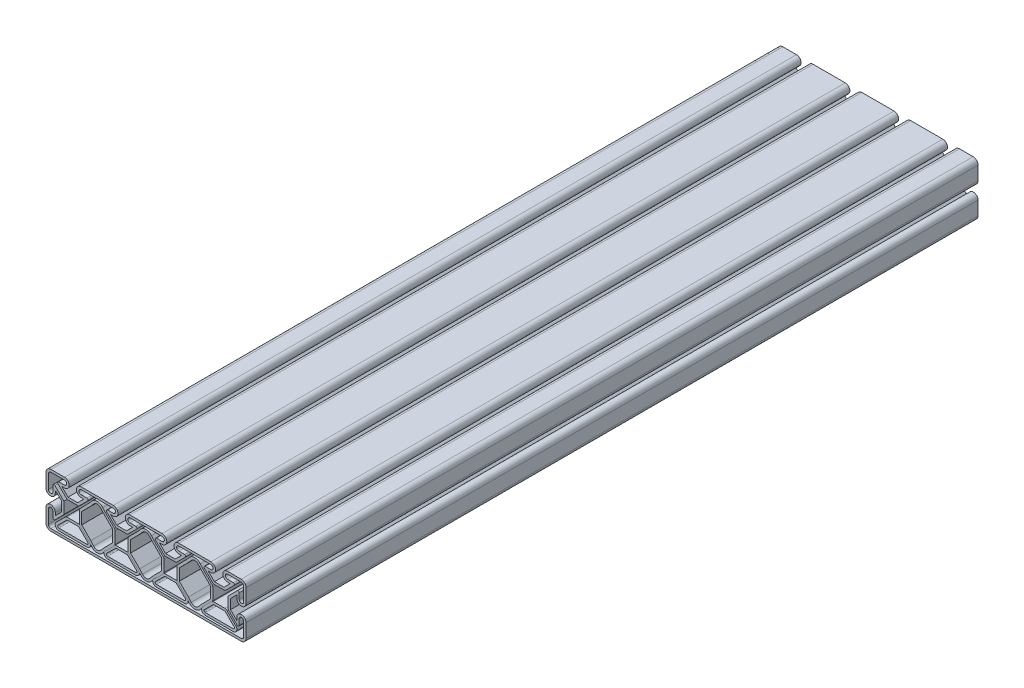
SolidWorks part; units mm, degrees
ref_plane "Alzado" through (0, 0, 0) normal (0, 0, 1) x (1, 0, 0)
ref_plane "Planta" through (0, 0, 0) normal (0, 1, 0) x (1, 0, 0)
ref_plane "Vista Lateral" through (0, 0, 0) normal (1, 0, 0) x (0, 0, -1)
ref_plane "Plano1" through (0, 0, 50) normal (0, 0, 1) x (1, 0, 0)
sketch "Croquis1" plane through (0, 0, 50) normal (0, 0, 1) x (1, 0, 0)
  line L0 (2.5926, -6.0784) -> (1.4258, -7.4138)
  line L1 (-1.5144, -7.3727) -> (-2.6752, -6.0808)
  line L2 (-2.6961, -6.061) -> (-6.3866, -2.3416)
  line L3 (-6.3926, -2.3074) -> (-6.3926, 2.3926)
  line L4 (-6.3866, 2.4268) -> (-2.6961, 6.1461)
  line L5 (-2.6778, 6.1636) -> (-1.511, 7.499)
  line L6 (1.4293, 7.4579) -> (2.59, 6.166)
  line L7 (2.611, 6.1461) -> (6.3014, 2.4268)
  line L8 (6.3074, 2.3926) -> (6.3074, -2.3074)
  line L9 (6.3014, -2.3416) -> (2.611, -6.061)
  line L10 (6.5574, 10.0426) -> (-6.6426, 10.0426)
  line L11 (-6.6426, 8.2426) -> (-4.2926, 8.2426)
  line L12 (-3.939, 7.389) -> (-7.5986, 3.7584)
  line L13 (-7.6926, 3.6926) -> (-12.3926, 3.6926)
  line L14 (-12.4866, 3.7584) -> (-16.1461, 7.389)
  line L15 (-15.7926, 8.2426) -> (-13.4426, 8.2426)
  line L16 (-13.4426, 10.0426) -> (-26.6426, 10.0426)
  line L17 (-26.6426, 8.2426) -> (-24.2926, 8.2426)
  line L18 (-23.939, 7.389) -> (-27.5986, 3.7584)
  line L19 (-27.6926, 3.6926) -> (-32.3926, 3.6926)
  line L20 (-32.4866, 3.7584) -> (-36.1461, 7.389)
  line L21 (-35.7926, 8.2426) -> (-33.4426, 8.2426)
  line L22 (-33.4426, 10.0426) -> (-39.0426, 10.0426)
  line L23 (-40.0426, 9.0426) -> (-40.0426, 3.4426)
  line L24 (-38.2426, 3.4426) -> (-38.2426, 5.7926)
  line L25 (-37.389, 6.1461) -> (-33.6986, 2.4268)
  line L26 (-33.6926, 2.3926) -> (-33.6926, -2.3074)
  line L27 (-33.6986, -2.3416) -> (-37.389, -6.061)
  line L28 (-38.2426, -5.7074) -> (-38.2426, -3.3574)
  line L29 (-40.0426, -3.3574) -> (-40.0426, -8.9574)
  line L30 (-39.0426, -9.9574) -> (-33.4426, -9.9574)
  line L31 (-33.4426, -8.1574) -> (-35.7926, -8.1574)
  line L32 (-36.1461, -7.3039) -> (-32.4866, -3.6732)
  line L33 (-32.3926, -3.6074) -> (-27.6926, -3.6074)
  line L34 (-27.5986, -3.6732) -> (-23.939, -7.3039)
  line L35 (-24.2926, -8.1574) -> (-26.6426, -8.1574)
  line L36 (-26.6426, -9.9574) -> (-13.4426, -9.9574)
  line L37 (-13.4426, -8.1574) -> (-15.7926, -8.1574)
  line L38 (-16.1461, -7.3039) -> (-12.4866, -3.6732)
  line L39 (-12.3926, -3.6074) -> (-7.6926, -3.6074)
  line L40 (-7.5986, -3.6732) -> (-3.939, -7.3039)
  line L41 (-4.2926, -8.1574) -> (-6.6426, -8.1574)
  line L42 (-6.6426, -9.9574) -> (6.5574, -9.9574)
  line L43 (6.5574, -8.1574) -> (4.2074, -8.1574)
  line L44 (3.8539, -7.3039) -> (7.5134, -3.6732)
  line L45 (7.6074, -3.6074) -> (12.3074, -3.6074)
  line L46 (12.4014, -3.6732) -> (16.061, -7.3039)
  line L47 (15.7074, -8.1574) -> (13.3574, -8.1574)
  line L48 (13.3574, -9.9574) -> (26.5574, -9.9574)
  line L49 (26.5574, -8.1574) -> (24.2074, -8.1574)
  line L50 (23.8539, -7.3039) -> (27.5134, -3.6732)
  line L51 (27.6074, -3.6074) -> (32.3074, -3.6074)
  line L52 (32.4014, -3.6732) -> (36.061, -7.3039)
  line L53 (35.7074, -8.1574) -> (33.3574, -8.1574)
  line L54 (33.3574, -9.9574) -> (38.9574, -9.9574)
  line L55 (39.9574, -8.9574) -> (39.9574, -3.3574)
  line L56 (38.1574, -3.3574) -> (38.1574, -5.7074)
  line L57 (37.3039, -6.061) -> (33.6134, -2.3416)
  line L58 (33.6074, -2.3074) -> (33.6074, 2.3926)
  line L59 (33.6134, 2.4268) -> (37.3039, 6.1461)
  line L60 (38.1574, 5.7926) -> (38.1574, 3.4426)
  line L61 (39.9574, 3.4426) -> (39.9574, 9.0426)
  line L62 (38.9574, 10.0426) -> (33.3574, 10.0426)
  line L63 (33.3574, 8.2426) -> (35.7074, 8.2426)
  line L64 (36.061, 7.389) -> (32.4014, 3.7584)
  line L65 (32.3074, 3.6926) -> (27.6074, 3.6926)
  line L66 (27.5134, 3.7584) -> (23.8539, 7.389)
  line L67 (24.2074, 8.2426) -> (26.5574, 8.2426)
  line L68 (26.5574, 10.0426) -> (13.3574, 10.0426)
  line L69 (13.3574, 8.2426) -> (15.7074, 8.2426)
  line L70 (16.061, 7.389) -> (12.4014, 3.7584)
  line L71 (12.3074, 3.6926) -> (7.6074, 3.6926)
  line L72 (7.5134, 3.7584) -> (3.8539, 7.389)
  line L73 (4.2074, 8.2426) -> (6.5574, 8.2426)
  line L74 (-17.4074, -6.0784) -> (-18.5742, -7.4138)
  line L75 (-21.5144, -7.3727) -> (-22.6752, -6.0808)
  line L76 (-22.6961, -6.061) -> (-26.3866, -2.3416)
  line L77 (-26.3926, -2.3074) -> (-26.3926, 2.3926)
  line L78 (-26.3866, 2.4268) -> (-22.6961, 6.1461)
  line L79 (-22.6778, 6.1636) -> (-21.511, 7.499)
  line L80 (-18.5707, 7.4579) -> (-17.41, 6.166)
  line L81 (-17.389, 6.1461) -> (-13.6986, 2.4268)
  line L82 (-13.6926, 2.3926) -> (-13.6926, -2.3074)
  line L83 (-13.6986, -2.3416) -> (-17.389, -6.061)
  line L84 (17.3222, 6.1636) -> (18.489, 7.499)
  line L85 (21.4293, 7.4579) -> (22.59, 6.166)
  line L86 (22.611, 6.1461) -> (26.3014, 2.4268)
  line L87 (26.3074, 2.3926) -> (26.3074, -2.3074)
  line L88 (26.3014, -2.3416) -> (22.611, -6.061)
  line L89 (22.5926, -6.0784) -> (21.4258, -7.4138)
  line L90 (18.4856, -7.3727) -> (17.3248, -6.0808)
  line L91 (17.3039, -6.061) -> (13.6134, -2.3416)
  line L92 (13.6074, -2.3074) -> (13.6074, 2.3926)
  line L93 (13.6134, 2.4268) -> (17.3039, 6.1461)
  line L94 (-33.4426, -8.1574) -> (-26.6426, -8.1574)
  line L95 (-26.6426, -9.9574) -> (-33.4426, -9.9574)
  line L96 (26.5574, -8.1574) -> (33.3574, -8.1574)
  line L97 (33.3574, -9.9574) -> (26.5574, -9.9574)
  line L98 (-13.4426, -8.1574) -> (-6.6426, -8.1574)
  line L99 (-13.4426, -9.9574) -> (-6.6426, -9.9574)
  line L100 (6.5574, -8.1574) -> (13.3574, -8.1574)
  line L101 (6.5574, -9.9574) -> (13.3574, -9.9574)
  arc A0 (1.4258, -7.4138) -> (-1.5144, -7.3727) centre (-0.0284, -6.257) cw
  arc A1 (-2.6752, -6.0808) -> (-2.6961, -6.061) centre (-2.3426, -5.7074) cw
  arc A2 (-6.3866, -2.3416) -> (-6.3926, -2.3074) centre (-6.2926, -2.3074) cw
  arc A3 (-6.3926, 2.3926) -> (-6.3866, 2.4268) centre (-6.2926, 2.3926) cw
  arc A4 (-2.6961, 6.1461) -> (-2.6778, 6.1636) centre (-2.3426, 5.7926) cw
  arc A5 (-1.511, 7.499) -> (1.4293, 7.4579) centre (-0.0568, 6.3422) cw
  arc A6 (2.59, 6.166) -> (2.611, 6.1461) centre (2.2574, 5.7926) cw
  arc A7 (6.3014, 2.4268) -> (6.3074, 2.3926) centre (6.2074, 2.3926) cw
  arc A8 (6.3074, -2.3074) -> (6.3014, -2.3416) centre (6.2074, -2.3074) cw
  arc A9 (2.611, -6.061) -> (2.5926, -6.0784) centre (2.2574, -5.7074) cw
  arc A10 (6.5574, 8.2426) -> (6.5574, 10.0426) centre (6.5574, 9.1426) ccw
  arc A11 (-6.6426, 10.0426) -> (-6.6426, 8.2426) centre (-6.6426, 9.1426) ccw
  arc A12 (-4.2926, 8.2426) -> (-3.939, 7.389) centre (-4.2926, 7.7426) cw
  arc A13 (-7.5986, 3.7584) -> (-7.6926, 3.6926) centre (-7.6926, 3.7926) cw
  arc A14 (-12.3926, 3.6926) -> (-12.4866, 3.7584) centre (-12.3926, 3.7926) cw
  arc A15 (-16.1461, 7.389) -> (-15.7926, 8.2426) centre (-15.7926, 7.7426) cw
  arc A16 (-13.4426, 8.2426) -> (-13.4426, 10.0426) centre (-13.4426, 9.1426) ccw
  arc A17 (-26.6426, 10.0426) -> (-26.6426, 8.2426) centre (-26.6426, 9.1426) ccw
  arc A18 (-24.2926, 8.2426) -> (-23.939, 7.389) centre (-24.2926, 7.7426) cw
  arc A19 (-27.5986, 3.7584) -> (-27.6926, 3.6926) centre (-27.6926, 3.7926) cw
  arc A20 (-32.3926, 3.6926) -> (-32.4866, 3.7584) centre (-32.3926, 3.7926) cw
  arc A21 (-36.1461, 7.389) -> (-35.7926, 8.2426) centre (-35.7926, 7.7426) cw
  arc A22 (-33.4426, 8.2426) -> (-33.4426, 10.0426) centre (-33.4426, 9.1426) ccw
  arc A23 (-39.0426, 10.0426) -> (-40.0426, 9.0426) centre (-39.0426, 9.0426) ccw
  arc A24 (-40.0426, 3.4426) -> (-38.2426, 3.4426) centre (-39.1426, 3.4426) ccw
  arc A25 (-38.2426, 5.7926) -> (-37.389, 6.1461) centre (-37.7426, 5.7926) cw
  arc A26 (-33.6986, 2.4268) -> (-33.6926, 2.3926) centre (-33.7926, 2.3926) cw
  arc A27 (-33.6926, -2.3074) -> (-33.6986, -2.3416) centre (-33.7926, -2.3074) cw
  arc A28 (-37.389, -6.061) -> (-38.2426, -5.7074) centre (-37.7426, -5.7074) cw
  arc A29 (-38.2426, -3.3574) -> (-40.0426, -3.3574) centre (-39.1426, -3.3574) ccw
  arc A30 (-40.0426, -8.9574) -> (-39.0426, -9.9574) centre (-39.0426, -8.9574) ccw
  arc A31 (-35.7926, -8.1574) -> (-36.1461, -7.3039) centre (-35.7926, -7.6574) cw
  arc A32 (-32.4866, -3.6732) -> (-32.3926, -3.6074) centre (-32.3926, -3.7074) cw
  arc A33 (-27.6926, -3.6074) -> (-27.5986, -3.6732) centre (-27.6926, -3.7074) cw
  arc A34 (-23.939, -7.3039) -> (-24.2926, -8.1574) centre (-24.2926, -7.6574) cw
  arc A35 (-15.7926, -8.1574) -> (-16.1461, -7.3039) centre (-15.7926, -7.6574) cw
  arc A36 (-12.4866, -3.6732) -> (-12.3926, -3.6074) centre (-12.3926, -3.7074) cw
  arc A37 (-7.6926, -3.6074) -> (-7.5986, -3.6732) centre (-7.6926, -3.7074) cw
  arc A38 (-3.939, -7.3039) -> (-4.2926, -8.1574) centre (-4.2926, -7.6574) cw
  arc A39 (4.2074, -8.1574) -> (3.8539, -7.3039) centre (4.2074, -7.6574) cw
  arc A40 (7.5134, -3.6732) -> (7.6074, -3.6074) centre (7.6074, -3.7074) cw
  arc A41 (12.3074, -3.6074) -> (12.4014, -3.6732) centre (12.3074, -3.7074) cw
  arc A42 (16.061, -7.3039) -> (15.7074, -8.1574) centre (15.7074, -7.6574) cw
  arc A43 (24.2074, -8.1574) -> (23.8539, -7.3039) centre (24.2074, -7.6574) cw
  arc A44 (27.5134, -3.6732) -> (27.6074, -3.6074) centre (27.6074, -3.7074) cw
  arc A45 (32.3074, -3.6074) -> (32.4014, -3.6732) centre (32.3074, -3.7074) cw
  arc A46 (36.061, -7.3039) -> (35.7074, -8.1574) centre (35.7074, -7.6574) cw
  arc A47 (38.9574, -9.9574) -> (39.9574, -8.9574) centre (38.9574, -8.9574) ccw
  arc A48 (39.9574, -3.3574) -> (38.1574, -3.3574) centre (39.0574, -3.3574) ccw
  arc A49 (38.1574, -5.7074) -> (37.3039, -6.061) centre (37.6574, -5.7074) cw
  arc A50 (33.6134, -2.3416) -> (33.6074, -2.3074) centre (33.7074, -2.3074) cw
  arc A51 (33.6074, 2.3926) -> (33.6134, 2.4268) centre (33.7074, 2.3926) cw
  arc A52 (37.3039, 6.1461) -> (38.1574, 5.7926) centre (37.6574, 5.7926) cw
  arc A53 (38.1574, 3.4426) -> (39.9574, 3.4426) centre (39.0574, 3.4426) ccw
  arc A54 (39.9574, 9.0426) -> (38.9574, 10.0426) centre (38.9574, 9.0426) ccw
  arc A55 (33.3574, 10.0426) -> (33.3574, 8.2426) centre (33.3574, 9.1426) ccw
  arc A56 (35.7074, 8.2426) -> (36.061, 7.389) centre (35.7074, 7.7426) cw
  arc A57 (32.4014, 3.7584) -> (32.3074, 3.6926) centre (32.3074, 3.7926) cw
  arc A58 (27.6074, 3.6926) -> (27.5134, 3.7584) centre (27.6074, 3.7926) cw
  arc A59 (23.8539, 7.389) -> (24.2074, 8.2426) centre (24.2074, 7.7426) cw
  arc A60 (26.5574, 8.2426) -> (26.5574, 10.0426) centre (26.5574, 9.1426) ccw
  arc A61 (13.3574, 10.0426) -> (13.3574, 8.2426) centre (13.3574, 9.1426) ccw
  arc A62 (15.7074, 8.2426) -> (16.061, 7.389) centre (15.7074, 7.7426) cw
  arc A63 (12.4014, 3.7584) -> (12.3074, 3.6926) centre (12.3074, 3.7926) cw
  arc A64 (7.6074, 3.6926) -> (7.5134, 3.7584) centre (7.6074, 3.7926) cw
  arc A65 (3.8539, 7.389) -> (4.2074, 8.2426) centre (4.2074, 7.7426) cw
  arc A66 (-18.5742, -7.4138) -> (-21.5144, -7.3727) centre (-20.0284, -6.257) cw
  arc A67 (-22.6752, -6.0808) -> (-22.6961, -6.061) centre (-22.3426, -5.7074) cw
  arc A68 (-26.3866, -2.3416) -> (-26.3926, -2.3074) centre (-26.2926, -2.3074) cw
  arc A69 (-26.3926, 2.3926) -> (-26.3866, 2.4268) centre (-26.2926, 2.3926) cw
  arc A70 (-22.6961, 6.1461) -> (-22.6778, 6.1636) centre (-22.3426, 5.7926) cw
  arc A71 (-21.511, 7.499) -> (-18.5707, 7.4579) centre (-20.0568, 6.3422) cw
  arc A72 (-17.41, 6.166) -> (-17.389, 6.1461) centre (-17.7426, 5.7926) cw
  arc A73 (-13.6986, 2.4268) -> (-13.6926, 2.3926) centre (-13.7926, 2.3926) cw
  arc A74 (-13.6926, -2.3074) -> (-13.6986, -2.3416) centre (-13.7926, -2.3074) cw
  arc A75 (-17.389, -6.061) -> (-17.4074, -6.0784) centre (-17.7426, -5.7074) cw
  arc A76 (18.489, 7.499) -> (21.4293, 7.4579) centre (19.9432, 6.3422) cw
  arc A77 (22.59, 6.166) -> (22.611, 6.1461) centre (22.2574, 5.7926) cw
  arc A78 (26.3014, 2.4268) -> (26.3074, 2.3926) centre (26.2074, 2.3926) cw
  arc A79 (26.3074, -2.3074) -> (26.3014, -2.3416) centre (26.2074, -2.3074) cw
  arc A80 (22.611, -6.061) -> (22.5926, -6.0784) centre (22.2574, -5.7074) cw
  arc A81 (21.4258, -7.4138) -> (18.4856, -7.3727) centre (19.9716, -6.257) cw
  arc A82 (17.3248, -6.0808) -> (17.3039, -6.061) centre (17.6574, -5.7074) cw
  arc A83 (13.6134, -2.3416) -> (13.6074, -2.3074) centre (13.7074, -2.3074) cw
  arc A84 (13.6074, 2.3926) -> (13.6134, 2.4268) centre (13.7074, 2.3926) cw
  arc A85 (17.3039, 6.1461) -> (17.3222, 6.1636) centre (17.6574, 5.7926) cw
  dimension "D12" = 1
  dimension "D23" = 0.9
  dimension "D24" = 0.9
  dimension "D25" = 0.9
  dimension "D26" = 0.5
  dimension "D1" = 18
  dimension "D2" = 78
  dimension "D3" = 5.6
  dimension "D4" = 2.35
  dimension "D5" = 6.8
  dimension "D6" = 13.2
  dimension "D7" = 13.2
  dimension "D8" = 13.2
  dimension "D9" = 4.7
  dimension "D10" = 5.2395
  dimension "D11" = 5.155
  dimension "D13" = 5.155
  dimension "D14" = 3.6306
  dimension "D15" = 6.8
  dimension "D16" = 13.2
  dimension "D17" = 13.2
  dimension "D18" = 6.8
  dimension "D19" = 6.8
  dimension "D20" = 13.2
  dimension "D21" = 6.8
  dimension "D22" = 5.6
extrude "Extruir-Lámina3" add sketch "Croquis1" along normal blind 300 thin thin type one direction wall 1
